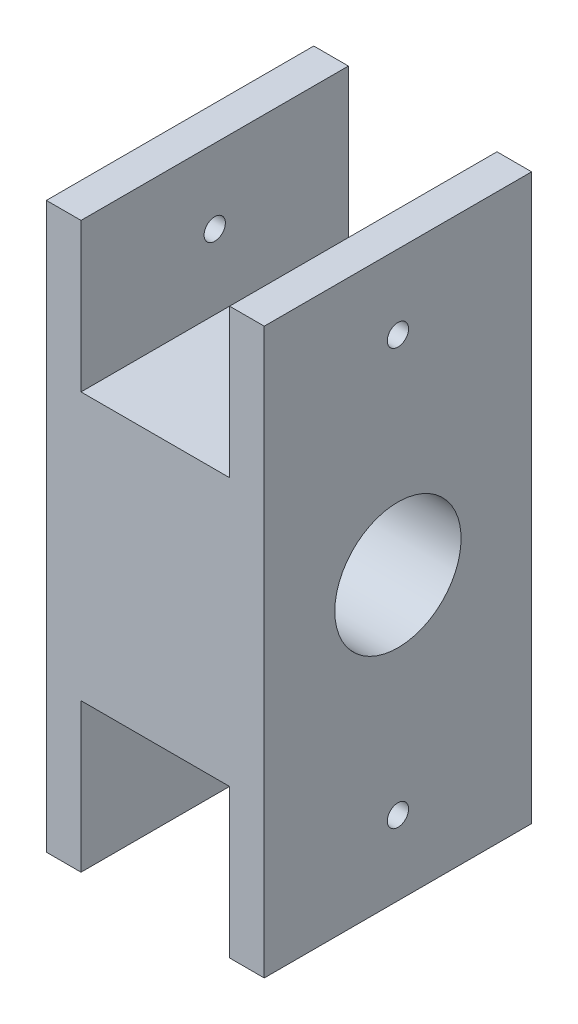
SolidWorks part; units mm, degrees
ref_plane "Front Plane" through (0, 0, 0) normal (0, 0, 1) x (1, 0, 0)
ref_plane "Top Plane" through (0, 0, 0) normal (0, 1, 0) x (1, 0, 0)
ref_plane "Right Plane" through (0, 0, 0) normal (1, 0, 0) x (0, 0, -1)
sketch "Sketch1" plane through (0, 0, 0) normal (0, 0, 1) x (1, 0, 0)
  line L0 (0, -1426.5537) -> (0, 69901.1317) construction
  line L1 (0, 0) -> (71327.6854, 0) construction
  line L2 (-22, 57) -> (-15, 57)
  line L3 (-15, 57) -> (-15, 27)
  line L4 (-15, 27) -> (15, 27)
  line L5 (15, 27) -> (15, 57)
  line L6 (15, 57) -> (22, 57)
  line L7 (22, 57) -> (22, -57)
  line L8 (22, -57) -> (15, -57)
  line L9 (15, -57) -> (15, -27)
  line L10 (15, -27) -> (-15, -27)
  line L11 (-15, -27) -> (-15, -57)
  line L12 (-15, -57) -> (-22, -57)
  line L13 (-22, -57) -> (-22, 57)
  point P9 (0, -27)
  point P18 (0, 27)
  point P19 (22, 0)
  point P20 (-22, 0)
  dimension "D1" = 30
  dimension "D2" = 7
  dimension "D3" = 54
extrude "Boss-Extrude1" add sketch "Sketch1" along normal blind 54
sketch "Sketch2" plane through (-22, 0, 0) normal (-1, 0, 0) x (0, 0, 1)
  line L0 (54, -57) -> (0, -57) construction
  line L1 (54, 57) -> (54, -57) construction
  line L2 (0, 57) -> (0, -57) construction
  line L3 (54, 57) -> (0, 57) construction
  line L4 (54, -57) -> (0, -57) construction
  line L5 (54, 57) -> (54, -57) construction
  line L6 (0, 57) -> (0, -57) construction
  line L7 (54, 57) -> (0, 57) construction
  line L8 (27, 57) -> (27, -57) construction
  line L9 (0, 42) -> (54, 42) construction
  line L10 (0, -42) -> (54, -42) construction
  point P10 (27, -42)
  point P11 (27, 42)
  dimension "D1" = 15
  dimension "D2" = 15
hole_wizard "Hole1" positions "Sketch2" profile "Sketch3" legacy end condition through all
sketch "Sketch3" plane through (-22, 42, 27) normal (0, 1, 0) x (0, 0, 1)
  line L0 (0, 0) -> (0, 44)
  line L1 (0, 44) -> (2.15, 44)
  line L2 (2.15, 44) -> (2.15, 0)
  line L3 (2.15, 0) -> (0, 0)
  line L4 (0, 110) -> (0, -10) construction
  dimension "Diameter" = 4.3
  dimension "Depth" = 44
sketch "Sketch4" plane through (-22, 0, 0) normal (-1, 0, 0) x (0, 0, 1)
  line L0 (0, 0) -> (54, 0) construction
  line L1 (54, 57) -> (54, -57) construction
  line L2 (27, 57) -> (27, -57) construction
  line L3 (54, 57) -> (0, 57) construction
  line L4 (54, -57) -> (0, -57) construction
  point P11 (27, 0)
hole_wizard "Hole2" positions "Sketch4" profile "Sketch5" legacy end condition through all
sketch "Sketch5" plane through (-22, 0, 27) normal (0, 1, 0) x (0, 0, 1)
  line L0 (0, 0) -> (0, 44)
  line L1 (0, 44) -> (12.75, 44)
  line L2 (12.75, 44) -> (12.75, 12)
  line L3 (12.75, 12) -> (20, 12)
  line L4 (20, 12) -> (20, 0)
  line L5 (20, 0) -> (0, 0)
  line L6 (0, 110) -> (0, -10) construction
  dimension "Depth" = 44
  dimension "Diameter" = 25.5
  dimension "C-Bore Diameter" = 40
  dimension "C-Bore Depth" = 12
equation "\"t_wall\" = 7mm"
equation "\"d_bearing\"= 40mm"
equation "\"w_extrusion\" = 30mm"
equation "\"D1@Sketch1\"=\"w_extrusion\""
equation "\"D2@Sketch1\"=\"t_wall\""
equation "\"D3@Sketch1\"=\"d_bearing\" +\"t_wall\" * 2"
equation "\"D1@Boss-Extrude1\"=\"d_bearing\"+\"t_wall\" *2"
equation "\"d_mount\"= 4.3mm"
equation "\"D1@Sketch2\"=\"w_extrusion\"/2"
equation "\"D2@Sketch2\"=\"w_extrusion\"/2"
equation "\"Diameter@Sketch3\"=\"d_mount\""
equation "\"h_bearing\"= 12mm"
equation "\"C-Bore Diameter@Sketch5\"=\"d_bearing\""
equation "\"d_flange\"= \"d_shaft\" * 1.5"
equation "\"Diameter@Sketch5\"=\"d_flange\""
equation "\"C-Bore Depth@Sketch5\"=\"h_bearing\""
equation "\"d_shaft\"= 17mm"
